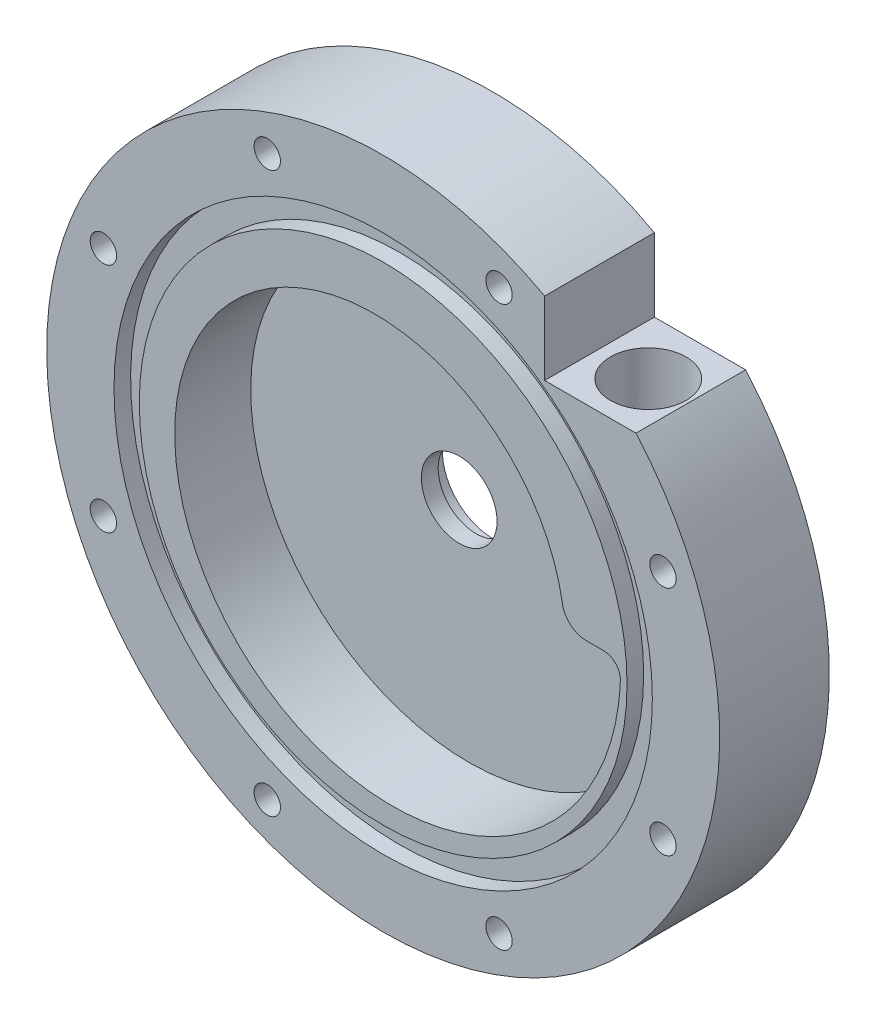
SolidWorks part; units mm, degrees
material "6061-T6 (SS)"
ref_plane "Front Plane" through (0, 0, 0) normal (0, 0, 1) x (1, 0, 0)
ref_plane "Top Plane" through (0, 0, 0) normal (0, 1, 0) x (1, 0, 0)
ref_plane "Right Plane" through (0, 0, 0) normal (1, 0, 0) x (0, 0, -1)
sketch "Sketch22" plane through (0, 0, 0) normal (0, 1, 0) x (1, 0, 0)
  line L0 (-25.4, 0) -> (-7.1437, 0)
  line L1 (-25.4, 0) -> (-25.4, -14.351)
  line L2 (-9.525, 6.35) -> (-9.525, 3.175)
  line L3 (-25.4, -14.351) -> (-63.5, -14.351)
  line L4 (-63.5, -14.351) -> (-63.5, 6.35)
  line L6 (-9.525, 3.175) -> (-7.1437, 3.175)
  line L9 (-9.525, 6.35) -> (-63.5, 6.35)
  line L10 (0, 0) -> (0, 9.525) construction
  line L11 (-7.1437, 3.175) -> (-7.1437, 0)
  dimension "D1" = 6.35
  dimension "D2" = 3.175
  dimension "D3" = 14.351
  dimension "D4" = 19.05
  dimension "D5" = 50.8
  dimension "D6" = 127
  dimension "D7" = 14.2875
revolve "Main Body" add sketch "Sketch22" angle 360 about L10
curve "Volute Spiral"
sketch "Sketch23" plane through (0, 0, 0) normal (0, 0, 1) x (1, 0, 0)
  line L1 (38.3384, 3.3047) -> (41.5935, 3.3047)
  arc A5 (34.2618, 0) -> (35.1661, 0) centre (34.714, -0.0185) ccw
  arc A6 (35.1661, 0) -> (38.3384, 3.3047) centre (38.3384, 0.1297) cw
  arc A7 (41.5935, 3.3047) -> (44.7632, 0) centre (41.5935, 0.1322) cw
  spline S1 degree 3 poles (2030.2811, -117.0653) (22.7633, -27.2168) (33.8126, -13.6289) (34.2778, 0.4312) (34.2837, 0.647) (34.2927, 1.0788) (34.2982, 2.0882) (34.2447, 3.6037) (34.0848, 5.4046) (33.8442, 7.1278) (33.5167, 8.8404) (33.1027, 10.5382) (32.6028, 12.2167) (32.018, 13.8717) (31.3492, 15.4988) (30.5978, 17.0937) (29.7654, 18.6523) (28.8536, 20.1705) (27.8645, 21.6442) (26.8001, 23.0695) (25.6629, 24.4425) (24.4554, 25.7594) (23.1804, 27.0168) (21.8408, 28.2111) (20.4397, 29.3391) (18.9803, 30.3974) (17.4663, 31.3832) (15.901, 32.2936) (14.2884, 33.126) (12.6323, 33.8779) (10.9367, 34.5469) (9.2057, 35.1311) (7.4437, 35.6286) (5.6549, 36.0377) (3.8437, 36.3569) (2.0147, 36.5852) (0.1725, 36.7214) (-1.6783, 36.7648) (-3.533, 36.7149) (-5.387, 36.5715) (-7.2355, 36.3344) (-9.0737, 36.0038) (-10.8971, 35.5803) (-12.7007, 35.0643) (-14.48, 34.457) (-16.2304, 33.7593) (-17.9471, 32.9726) (-19.6258, 32.0987) (-21.262, 31.1393) (-22.8513, 30.0964) (-24.3894, 28.9724) (-25.8723, 27.7699) (-27.2958, 26.4914) (-28.6562, 25.1399) (-29.9497, 23.7185) (-31.1726, 22.2307) (-32.3216, 20.6797) (-33.3934, 19.0694) (-34.385, 17.4036) (-35.2934, 15.6863) (-36.116, 13.9216) (-36.8503, 12.1138) (-37.4941, 10.2673) (-38.0454, 8.3867) (-38.5022, 6.4766) (-38.8631, 4.5417) (-39.1267, 2.587) (-39.292, 0.6172) (-39.358, -1.3627) (-39.3242, -3.3477) (-39.1902, -5.3327) (-38.956, -7.3127) (-38.6217, -9.2826) (-38.1877, -11.2374) (-37.6547, -13.172) (-37.0237, -15.0814) (-36.2958, -16.9606) (-35.4725, -18.8047) (-34.5554, -20.6088) (-33.5465, -22.3683) (-32.448, -24.0784) (-31.2623, -25.7345) (-29.9921, -27.3322) (-28.6401, -28.8672) (-27.2096, -30.3353) (-25.7038, -31.7324) (-24.1262, -33.0548) (-22.4806, -34.2987) (-20.7709, -35.4607) (-19.0011, -36.5374) (-17.1755, -37.5256) (-15.2985, -38.4226) (-13.3748, -39.2257) (-11.4089, -39.9324) (-9.4058, -40.5405) (-7.3703, -41.048) (-5.3076, -41.4533) (-3.2227, -41.7548) (-1.1209, -41.9515) (0.9925, -42.0422) (3.1122, -42.0264) (5.2328, -41.9037) (7.349, -41.6739) (9.4552, -41.3371) (11.5462, -40.8938) (13.6164, -40.3447) (15.6606, -39.6907) (17.6735, -38.9331) (19.6497, -38.0733) (21.5841, -37.1132) (23.4715, -36.0547) (25.3071, -34.9002) (27.0859, -33.6522) (28.8031, -32.3134) (30.4541, -30.887) (32.0344, -29.3763) (33.5397, -27.7846) (34.9659, -26.1158) (36.309, -24.3737) (37.5652, -22.5626) (38.7311, -20.6867) (39.8032, -18.7505) (40.7784, -16.7589) (41.6539, -14.7165) (42.4271, -12.6284) (43.0955, -10.4997) (43.657, -8.3358) (44.1098, -6.1419) (44.4379, -4.0162) (44.6062, -2.4335) (44.6789, -1.4992) (44.7044, -1.1249) (44.7219, -0.8439) (44.7375, -0.5628) (45.566, 16.1056) (34.6961, 33.2048) (2043.9061, -40.4097) knots -0.16783 -0.16783 -0.16783 -0.16783 0.000871 0.001743 0.002614 0.003486 0.006976 0.014843 0.021852 0.028876 0.035916 0.042971 0.050042 0.057129 0.064232 0.07135 0.078484 0.085634 0.0928 0.099981 0.107179 0.114393 0.121623 0.128869 0.136131 0.143409 0.150703 0.158014 0.165341 0.172684 0.180044 0.187419 0.194812 0.20222 0.209645 0.217087 0.224545 0.232019 0.23951 0.247018 0.254542 0.262083 0.26964 0.277214 0.284805 0.292413 0.300037 0.307678 0.315336 0.32301 0.330702 0.33841 0.346135 0.353877 0.361636 0.369412 0.377205 0.385015 0.392841 0.400685 0.408546 0.416424 0.424319 0.432231 0.440161 0.448107 0.456071 0.464051 0.472049 0.480065 0.488097 0.496147 0.504214 0.512298 0.5204 0.528519 0.536655 0.544809 0.55298 0.561169 0.569375 0.577598 0.585839 0.594097 0.602373 0.610667 0.618977 0.627306 0.635652 0.644016 0.652397 0.660796 0.669212 0.677647 0.686099 0.694568 0.703055 0.71156 0.720083 0.728624 0.737182 0.745758 0.754352 0.762964 0.771593 0.780241 0.788906 0.797589 0.80629 0.815009 0.823746 0.832501 0.841274 0.850065 0.858874 0.867701 0.876546 0.885409 0.89429 0.903189 0.912106 0.921041 0.929995 0.938966 0.947956 0.956964 0.96599 0.975034 0.984097 0.992041 0.994314 0.995451 0.996587 0.997725 0.998862 1.198789 1.198789 1.198789 1.198789 only from (34.2618, 0) to (44.7632, 0) construction
  spline S2 degree 3 poles (34.2618, 0) (34.2648, 0.0718) (34.2707, 0.2156) (34.2778, 0.4312) (34.2837, 0.647) (34.2927, 1.0788) (34.2982, 2.0882) (34.2447, 3.6037) (34.0848, 5.4046) (33.8442, 7.1278) (33.5167, 8.8404) (33.1027, 10.5382) (32.6028, 12.2167) (32.018, 13.8717) (31.3492, 15.4988) (30.5978, 17.0937) (29.7654, 18.6523) (28.8536, 20.1705) (27.8645, 21.6442) (26.8001, 23.0695) (25.6629, 24.4425) (24.4554, 25.7594) (23.1804, 27.0168) (21.8408, 28.2111) (20.4397, 29.3391) (18.9803, 30.3974) (17.4663, 31.3832) (15.901, 32.2936) (14.2884, 33.126) (12.6323, 33.8779) (10.9367, 34.5469) (9.2057, 35.1311) (7.4437, 35.6286) (5.6549, 36.0377) (3.8437, 36.3569) (2.0147, 36.5852) (0.1725, 36.7214) (-1.6783, 36.7648) (-3.533, 36.7149) (-5.387, 36.5715) (-7.2355, 36.3344) (-9.0737, 36.0038) (-10.8971, 35.5803) (-12.7007, 35.0643) (-14.48, 34.457) (-16.2304, 33.7593) (-17.9471, 32.9726) (-19.6258, 32.0987) (-21.262, 31.1393) (-22.8513, 30.0964) (-24.3894, 28.9724) (-25.8723, 27.7699) (-27.2958, 26.4914) (-28.6562, 25.1399) (-29.9497, 23.7185) (-31.1726, 22.2307) (-32.3216, 20.6797) (-33.3934, 19.0694) (-34.385, 17.4036) (-35.2934, 15.6863) (-36.116, 13.9216) (-36.8503, 12.1138) (-37.4941, 10.2673) (-38.0454, 8.3867) (-38.5022, 6.4766) (-38.8631, 4.5417) (-39.1267, 2.587) (-39.292, 0.6172) (-39.358, -1.3627) (-39.3242, -3.3477) (-39.1902, -5.3327) (-38.956, -7.3127) (-38.6217, -9.2826) (-38.1877, -11.2374) (-37.6547, -13.172) (-37.0237, -15.0814) (-36.2958, -16.9606) (-35.4725, -18.8047) (-34.5554, -20.6088) (-33.5465, -22.3683) (-32.448, -24.0784) (-31.2623, -25.7345) (-29.9921, -27.3322) (-28.6401, -28.8672) (-27.2096, -30.3353) (-25.7038, -31.7324) (-24.1262, -33.0548) (-22.4806, -34.2987) (-20.7709, -35.4607) (-19.0011, -36.5374) (-17.1755, -37.5256) (-15.2985, -38.4226) (-13.3748, -39.2257) (-11.4089, -39.9324) (-9.4058, -40.5405) (-7.3703, -41.048) (-5.3076, -41.4533) (-3.2227, -41.7548) (-1.1209, -41.9515) (0.9925, -42.0422) (3.1122, -42.0264) (5.2328, -41.9037) (7.349, -41.6739) (9.4552, -41.3371) (11.5462, -40.8938) (13.6164, -40.3447) (15.6606, -39.6907) (17.6735, -38.9331) (19.6497, -38.0733) (21.5841, -37.1132) (23.4715, -36.0547) (25.3071, -34.9002) (27.0859, -33.6522) (28.8031, -32.3134) (30.4541, -30.887) (32.0344, -29.3763) (33.5397, -27.7846) (34.9659, -26.1158) (36.309, -24.3737) (37.5652, -22.5626) (38.7311, -20.6867) (39.8032, -18.7505) (40.7784, -16.7589) (41.6539, -14.7165) (42.4271, -12.6284) (43.0955, -10.4997) (43.657, -8.3358) (44.1098, -6.1419) (44.4379, -4.0162) (44.6062, -2.4335) (44.6789, -1.4992) (44.7044, -1.1249) (44.7219, -0.8439) (44.7375, -0.5628) (44.7515, -0.2815) (44.7593, -0.0938) (44.7632, 0) knots 0 0 0 0 0.000871 0.001743 0.002614 0.003486 0.006976 0.014843 0.021852 0.028876 0.035916 0.042971 0.050042 0.057129 0.064232 0.07135 0.078484 0.085634 0.0928 0.099981 0.107179 0.114393 0.121623 0.128869 0.136131 0.143409 0.150703 0.158014 0.165341 0.172684 0.180044 0.187419 0.194812 0.20222 0.209645 0.217087 0.224545 0.232019 0.23951 0.247018 0.254542 0.262083 0.26964 0.277214 0.284805 0.292413 0.300037 0.307678 0.315336 0.32301 0.330702 0.33841 0.346135 0.353877 0.361636 0.369412 0.377205 0.385015 0.392841 0.400685 0.408546 0.416424 0.424319 0.432231 0.440161 0.448107 0.456071 0.464051 0.472049 0.480065 0.488097 0.496147 0.504214 0.512298 0.5204 0.528519 0.536655 0.544809 0.55298 0.561169 0.569375 0.577598 0.585839 0.594097 0.602373 0.610667 0.618977 0.627306 0.635652 0.644016 0.652397 0.660796 0.669212 0.677647 0.686099 0.694568 0.703055 0.71156 0.720083 0.728624 0.737182 0.745758 0.754352 0.762964 0.771593 0.780241 0.788906 0.797589 0.80629 0.815009 0.823746 0.832501 0.841274 0.850065 0.858874 0.867701 0.876546 0.885409 0.89429 0.903189 0.912106 0.921041 0.929995 0.938966 0.947956 0.956964 0.96599 0.975034 0.984097 0.992041 0.994314 0.995451 0.996587 0.997725 0.998862 1 1 1 1
  dimension "D1" = 0.9042
  dimension "D2" = 3.175
extrude "Volute Cut" cut sketch "Sketch23" along normal through all
ref_plane "Volute Height Plane" through (0, 0, 8.5801) normal (0, 0, 1) x (1, 0, 0)
sketch "Sketch25" plane through (0, 0, 8.5801) normal (0, 0, 1) x (1, 0, 0)
  line L0 (38.3384, 3.3047) -> (41.5935, 3.3047)
  arc A0 (34.2618, 0) -> (35.1661, 0) centre (34.714, -0.0185) ccw
  arc A7 (35.1661, 0) -> (38.3384, 3.3047) centre (38.3384, 0.1297) cw
  arc A8 (41.5935, 3.3047) -> (44.7632, 0) centre (41.5935, 0.1322) cw
  arc A10 (38.3384, 3.3047) -> (33.8292, 7.1291) centre (38.3384, 7.8752) cw
  spline S2 degree 3 poles (2030.2811, -117.0653) (22.7633, -27.2168) (33.8126, -13.6289) (34.2778, 0.4312) (34.2837, 0.647) (34.2927, 1.0788) (34.2982, 2.0882) (34.2447, 3.6037) (34.0848, 5.4046) (33.8442, 7.1278) (33.5167, 8.8404) (33.1027, 10.5382) (32.6028, 12.2167) (32.018, 13.8717) (31.3492, 15.4988) (30.5978, 17.0937) (29.7654, 18.6523) (28.8536, 20.1705) (27.8645, 21.6442) (26.8001, 23.0695) (25.6629, 24.4425) (24.4554, 25.7594) (23.1804, 27.0168) (21.8408, 28.2111) (20.4397, 29.3391) (18.9803, 30.3974) (17.4663, 31.3832) (15.901, 32.2936) (14.2884, 33.126) (12.6323, 33.8779) (10.9367, 34.5469) (9.2057, 35.1311) (7.4437, 35.6286) (5.6549, 36.0377) (3.8437, 36.3569) (2.0147, 36.5852) (0.1725, 36.7214) (-1.6783, 36.7648) (-3.533, 36.7149) (-5.387, 36.5715) (-7.2355, 36.3344) (-9.0737, 36.0038) (-10.8971, 35.5803) (-12.7007, 35.0643) (-14.48, 34.457) (-16.2304, 33.7593) (-17.9471, 32.9726) (-19.6258, 32.0987) (-21.262, 31.1393) (-22.8513, 30.0964) (-24.3894, 28.9724) (-25.8723, 27.7699) (-27.2958, 26.4914) (-28.6562, 25.1399) (-29.9497, 23.7185) (-31.1726, 22.2307) (-32.3216, 20.6797) (-33.3934, 19.0694) (-34.385, 17.4036) (-35.2934, 15.6863) (-36.116, 13.9216) (-36.8503, 12.1138) (-37.4941, 10.2673) (-38.0454, 8.3867) (-38.5022, 6.4766) (-38.8631, 4.5417) (-39.1267, 2.587) (-39.292, 0.6172) (-39.358, -1.3627) (-39.3242, -3.3477) (-39.1902, -5.3327) (-38.956, -7.3127) (-38.6217, -9.2826) (-38.1877, -11.2374) (-37.6547, -13.172) (-37.0237, -15.0814) (-36.2958, -16.9606) (-35.4725, -18.8047) (-34.5554, -20.6088) (-33.5465, -22.3683) (-32.448, -24.0784) (-31.2623, -25.7345) (-29.9921, -27.3322) (-28.6401, -28.8672) (-27.2096, -30.3353) (-25.7038, -31.7324) (-24.1262, -33.0548) (-22.4806, -34.2987) (-20.7709, -35.4607) (-19.0011, -36.5374) (-17.1755, -37.5256) (-15.2985, -38.4226) (-13.3748, -39.2257) (-11.4089, -39.9324) (-9.4058, -40.5405) (-7.3703, -41.048) (-5.3076, -41.4533) (-3.2227, -41.7548) (-1.1209, -41.9515) (0.9925, -42.0422) (3.1122, -42.0264) (5.2328, -41.9037) (7.349, -41.6739) (9.4552, -41.3371) (11.5462, -40.8938) (13.6164, -40.3447) (15.6606, -39.6907) (17.6735, -38.9331) (19.6497, -38.0733) (21.5841, -37.1132) (23.4715, -36.0547) (25.3071, -34.9002) (27.0859, -33.6522) (28.8031, -32.3134) (30.4541, -30.887) (32.0344, -29.3763) (33.5397, -27.7846) (34.9659, -26.1158) (36.309, -24.3737) (37.5652, -22.5626) (38.7311, -20.6867) (39.8032, -18.7505) (40.7784, -16.7589) (41.6539, -14.7165) (42.4271, -12.6284) (43.0955, -10.4997) (43.657, -8.3358) (44.1098, -6.1419) (44.4379, -4.0162) (44.6062, -2.4335) (44.6789, -1.4992) (44.7044, -1.1249) (44.7219, -0.8439) (44.7375, -0.5628) (45.566, 16.1056) (34.6961, 33.2048) (2043.9061, -40.4097) knots -0.16783 -0.16783 -0.16783 -0.16783 0.000871 0.001743 0.002614 0.003486 0.006976 0.014843 0.021852 0.028876 0.035916 0.042971 0.050042 0.057129 0.064232 0.07135 0.078484 0.085634 0.0928 0.099981 0.107179 0.114393 0.121623 0.128869 0.136131 0.143409 0.150703 0.158014 0.165341 0.172684 0.180044 0.187419 0.194812 0.20222 0.209645 0.217087 0.224545 0.232019 0.23951 0.247018 0.254542 0.262083 0.26964 0.277214 0.284805 0.292413 0.300037 0.307678 0.315336 0.32301 0.330702 0.33841 0.346135 0.353877 0.361636 0.369412 0.377205 0.385015 0.392841 0.400685 0.408546 0.416424 0.424319 0.432231 0.440161 0.448107 0.456071 0.464051 0.472049 0.480065 0.488097 0.496147 0.504214 0.512298 0.5204 0.528519 0.536655 0.544809 0.55298 0.561169 0.569375 0.577598 0.585839 0.594097 0.602373 0.610667 0.618977 0.627306 0.635652 0.644016 0.652397 0.660796 0.669212 0.677647 0.686099 0.694568 0.703055 0.71156 0.720083 0.728624 0.737182 0.745758 0.754352 0.762964 0.771593 0.780241 0.788906 0.797589 0.80629 0.815009 0.823746 0.832501 0.841274 0.850065 0.858874 0.867701 0.876546 0.885409 0.89429 0.903189 0.912106 0.921041 0.929995 0.938966 0.947956 0.956964 0.96599 0.975034 0.984097 0.992041 0.994314 0.995451 0.996587 0.997725 0.998862 1.198789 1.198789 1.198789 1.198789 only from (34.2618, 0) to (44.7632, 0) construction
  spline S3 degree 3 poles (34.2618, 0) (34.2648, 0.0718) (34.2707, 0.2156) (34.2778, 0.4312) (34.2837, 0.647) (34.2927, 1.0788) (34.2982, 2.0882) (34.2447, 3.6037) (34.0848, 5.4046) (33.8442, 7.1278) (33.5167, 8.8404) (33.1027, 10.5382) (32.6028, 12.2167) (32.018, 13.8717) (31.3492, 15.4988) (30.5978, 17.0937) (29.7654, 18.6523) (28.8536, 20.1705) (27.8645, 21.6442) (26.8001, 23.0695) (25.6629, 24.4425) (24.4554, 25.7594) (23.1804, 27.0168) (21.8408, 28.2111) (20.4397, 29.3391) (18.9803, 30.3974) (17.4663, 31.3832) (15.901, 32.2936) (14.2884, 33.126) (12.6323, 33.8779) (10.9367, 34.5469) (9.2057, 35.1311) (7.4437, 35.6286) (5.6549, 36.0377) (3.8437, 36.3569) (2.0147, 36.5852) (0.1725, 36.7214) (-1.6783, 36.7648) (-3.533, 36.7149) (-5.387, 36.5715) (-7.2355, 36.3344) (-9.0737, 36.0038) (-10.8971, 35.5803) (-12.7007, 35.0643) (-14.48, 34.457) (-16.2304, 33.7593) (-17.9471, 32.9726) (-19.6258, 32.0987) (-21.262, 31.1393) (-22.8513, 30.0964) (-24.3894, 28.9724) (-25.8723, 27.7699) (-27.2958, 26.4914) (-28.6562, 25.1399) (-29.9497, 23.7185) (-31.1726, 22.2307) (-32.3216, 20.6797) (-33.3934, 19.0694) (-34.385, 17.4036) (-35.2934, 15.6863) (-36.116, 13.9216) (-36.8503, 12.1138) (-37.4941, 10.2673) (-38.0454, 8.3867) (-38.5022, 6.4766) (-38.8631, 4.5417) (-39.1267, 2.587) (-39.292, 0.6172) (-39.358, -1.3627) (-39.3242, -3.3477) (-39.1902, -5.3327) (-38.956, -7.3127) (-38.6217, -9.2826) (-38.1877, -11.2374) (-37.6547, -13.172) (-37.0237, -15.0814) (-36.2958, -16.9606) (-35.4725, -18.8047) (-34.5554, -20.6088) (-33.5465, -22.3683) (-32.448, -24.0784) (-31.2623, -25.7345) (-29.9921, -27.3322) (-28.6401, -28.8672) (-27.2096, -30.3353) (-25.7038, -31.7324) (-24.1262, -33.0548) (-22.4806, -34.2987) (-20.7709, -35.4607) (-19.0011, -36.5374) (-17.1755, -37.5256) (-15.2985, -38.4226) (-13.3748, -39.2257) (-11.4089, -39.9324) (-9.4058, -40.5405) (-7.3703, -41.048) (-5.3076, -41.4533) (-3.2227, -41.7548) (-1.1209, -41.9515) (0.9925, -42.0422) (3.1122, -42.0264) (5.2328, -41.9037) (7.349, -41.6739) (9.4552, -41.3371) (11.5462, -40.8938) (13.6164, -40.3447) (15.6606, -39.6907) (17.6735, -38.9331) (19.6497, -38.0733) (21.5841, -37.1132) (23.4715, -36.0547) (25.3071, -34.9002) (27.0859, -33.6522) (28.8031, -32.3134) (30.4541, -30.887) (32.0344, -29.3763) (33.5397, -27.7846) (34.9659, -26.1158) (36.309, -24.3737) (37.5652, -22.5626) (38.7311, -20.6867) (39.8032, -18.7505) (40.7784, -16.7589) (41.6539, -14.7165) (42.4271, -12.6284) (43.0955, -10.4997) (43.657, -8.3358) (44.1098, -6.1419) (44.4379, -4.0162) (44.6062, -2.4335) (44.6789, -1.4992) (44.7044, -1.1249) (44.7219, -0.8439) (44.7375, -0.5628) (44.7515, -0.2815) (44.7593, -0.0938) (44.7632, 0) knots 0 0 0 0 0.000871 0.001743 0.002614 0.003486 0.006976 0.014843 0.021852 0.028876 0.035916 0.042971 0.050042 0.057129 0.064232 0.07135 0.078484 0.085634 0.0928 0.099981 0.107179 0.114393 0.121623 0.128869 0.136131 0.143409 0.150703 0.158014 0.165341 0.172684 0.180044 0.187419 0.194812 0.20222 0.209645 0.217087 0.224545 0.232019 0.23951 0.247018 0.254542 0.262083 0.26964 0.277214 0.284805 0.292413 0.300037 0.307678 0.315336 0.32301 0.330702 0.33841 0.346135 0.353877 0.361636 0.369412 0.377205 0.385015 0.392841 0.400685 0.408546 0.416424 0.424319 0.432231 0.440161 0.448107 0.456071 0.464051 0.472049 0.480065 0.488097 0.496147 0.504214 0.512298 0.5204 0.528519 0.536655 0.544809 0.55298 0.561169 0.569375 0.577598 0.585839 0.594097 0.602373 0.610667 0.618977 0.627306 0.635652 0.644016 0.652397 0.660796 0.669212 0.677647 0.686099 0.694568 0.703055 0.71156 0.720083 0.728624 0.737182 0.745758 0.754352 0.762964 0.771593 0.780241 0.788906 0.797589 0.80629 0.815009 0.823746 0.832501 0.841274 0.850065 0.858874 0.867701 0.876546 0.885409 0.89429 0.903189 0.912106 0.921041 0.929995 0.938966 0.947956 0.956964 0.96599 0.975034 0.984097 0.992041 0.994314 0.995451 0.996587 0.997725 0.998862 1 1 1 1
  dimension "D1" = 3.175
  dimension "D2" = 0.9042
extrude "Cap Cut" cut sketch "Sketch25" along normal through all contours S3 A0 A7 A10 | A0 S3 A8 L0 A7 region at (0.5826, -3.3219, 8.5801) region at (35.147, 2.7612, 8.5801)
sketch "Sketch28" plane through (0, 0, 14.351) normal (0, 0, 1) x (1, 0, 0)
  line L1 (30.48, 55.7065) -> (47.7054, 55.7065)
  line L2 (30.48, 55.7065) -> (30.48, 41.91)
  line L3 (30.48, 41.91) -> (47.7054, 41.91)
  line L4 (47.7054, 55.7065) -> (47.7054, 41.91)
  circle A1 centre (0, 0) radius 63.5 construction
  dimension "D1" = 41.91
  dimension "D2" = 30.48
extrude "Outlet Hole Cut" cut sketch "Sketch28" against normal through all
hole_wizard "Outlet Hole" positions "3DSketch2" profile "Sketch20" hole size "3/8" standard "ANSI Inch"
sketch3d "3DSketch2"
  line L0 (41.5935, 3.3047, 0) -> (38.3384, 3.3047, 8.5801) construction
  point P0 (39.966, 3.3047, 4.2901)
  point P11 (39.966, 3.3047, 4.2901)
  point P20 (39.966, 3.3047, 4.2901)
  point P22 (39.966, 41.91, 4.2901)
sketch "Sketch20" plane through (39.966, 41.91, 4.2901) normal (1, 0, 0) x (0, 0, 1)
  line L0 (0, 0) -> (0, 53.6616)
  line L1 (0, 53.6616) -> (4.7625, 50.8)
  line L2 (4.7625, 50.8) -> (4.7625, 0)
  line L5 (4.7625, 0) -> (0, 0)
  line L10 (0, 53.6616) -> (-4.7625, 50.8) construction
  line L11 (0, -6.35) -> (0, 107.95) construction
  dimension "Hole Dia." = 9.525
  dimension "Hole Depth" = 50.8
  dimension "Drill Angle" = 118
hole_wizard "Pipe Tap Drill for 3/8 Tap1" positions "3DSketch4" profile "Sketch29" hole size "3/8" standard "ANSI Inch"
sketch3d "3DSketch4"
  circle A0 centre (39.966, 41.91, 4.2901) radius 4.7625 construction
  point P0 (39.966, 41.91, 4.2901)
  point P6 (39.966, 46.6725, 4.2901)
sketch "Sketch29" plane through (39.966, 41.91, 4.2901) normal (1, 0, 0) x (0, 0, 1)
  line L0 (0, 0) -> (0, 16.9886)
  line L1 (0, 16.9886) -> (7.1374, 12.7)
  line L2 (7.1374, 12.7) -> (7.1374, 0)
  line L5 (7.1374, 0) -> (0, 0)
  line L10 (0, 16.9886) -> (-7.1374, 12.7) construction
  line L11 (0, -6.35) -> (0, 107.95) construction
  dimension "Hole Dia." = 14.2748
  dimension "Hole Depth" = 12.7
  dimension "Drill Angle" = 118
sketch "Sketch26" plane through (0, 0, 14.351) normal (0, 0, 1) x (1, 0, 0)
  line L0 (52.7997, -21.8704) -> (58.6664, -24.3004) construction
  line L1 (63.5, 0) -> (0, 0) construction
  circle A0 centre (52.7997, -21.8704) radius 2.4892
  circle A1 centre (0, 0) radius 63.5 construction
  dimension "D1" = 4.9784
  dimension "D2" = 6.35
  dimension "D3" = 22.5
extrude "Fastener Hole" cut sketch "Sketch26" against normal through all
pattern_circular "Fastener Holes" count 8 over 360 about axis through (0, 0, 0) along (0, 0, 1) of "Fastener Hole"
ref_axis "Axis1" through (0, 0, -6.35) along (0, 0, 1)
ref_plane "Plane1" through (0, 0, 0) normal (0, 1, 0) x (0, 0, 1)
sketch "Sketch16" plane through (0, 0, 14.351) normal (0, 0, 1) x (1, 0, 0)
  circle A0 centre (0, 0) radius 46.0248
  circle A1 centre (0, 0) radius 50.8
  dimension "D1" = 4.7752
  dimension "D2" = 101.6
extrude "O-Ring Groove" cut sketch "Sketch16" against normal blind 3.1369
